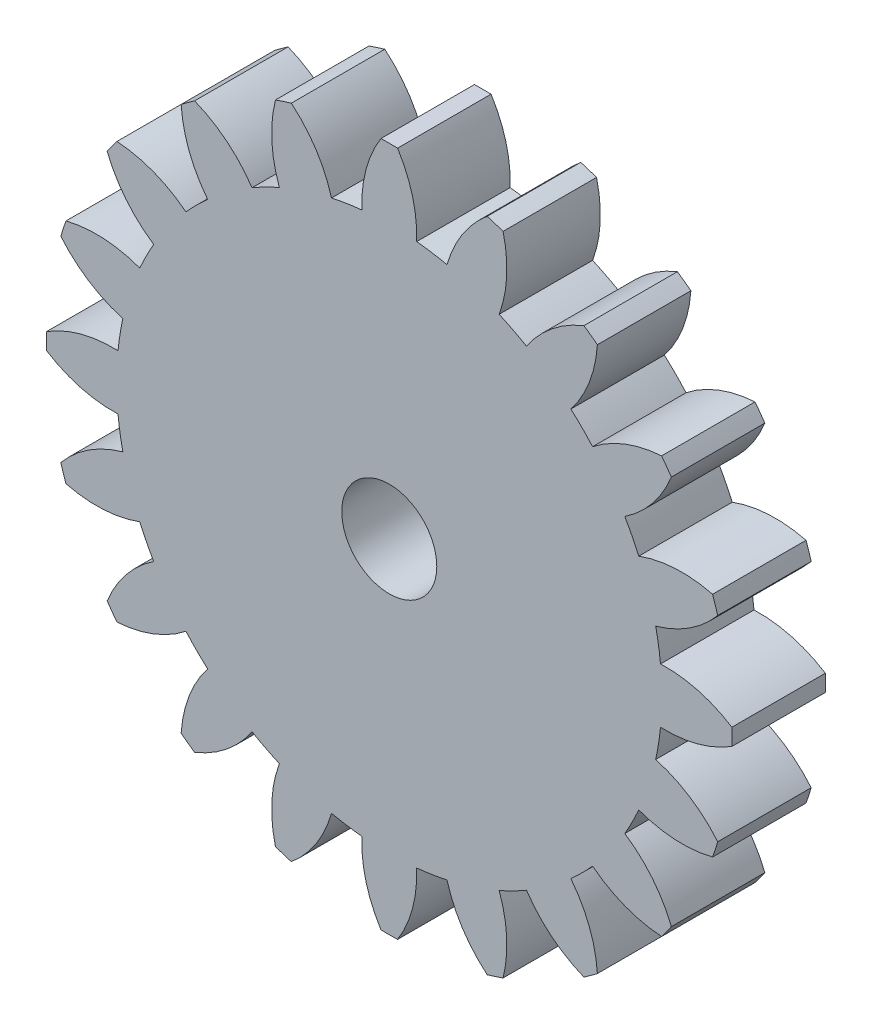
SolidWorks part; units mm, degrees
ref_plane "Front Plane" through (0, 0, 0) normal (0, 0, 1) x (1, 0, 0)
ref_plane "Top Plane" through (0, 0, 0) normal (0, 1, 0) x (1, 0, 0)
ref_plane "Right Plane" through (0, 0, 0) normal (1, 0, 0) x (0, 0, -1)
sketch "Sketch1" plane through (0, 0, 0) normal (0, 0, 1) x (1, 0, 0)
  point P0 (0, 22)
  arc B0 (12.4951, 18.1072) -> (8.8104, 15.1192) centre (15.4651, 10.679) ccw
  arc B1 (8.8104, 15.1192) -> (7.0531, 16.0147) centre (0, 0) ccw
  arc B2 (7.0531, 16.0147) -> (7.3046, 20.7519) centre (-0.4507, 18.7884) ccw
  arc B3 (7.3046, 20.7519) -> (6.2881, 21.0822) centre (0, 0) ccw
  arc B4 (6.2881, 21.0822) -> (3.7071, 17.1018) centre (11.4082, 14.9353) ccw
  arc B5 (3.7071, 17.1018) -> (1.7591, 17.4104) centre (0, 0) ccw
  arc B6 (1.7591, 17.4104) -> (0.5344, 21.9935) centre (-6.2346, 17.7296) ccw
  arc B7 (0.5344, 21.9935) -> (-0.5344, 21.9935) centre (0, 0) ccw
  arc B8 (-0.5344, 21.9935) -> (-1.7591, 17.4104) centre (6.2346, 17.7296) ccw
  arc B9 (-1.7591, 17.4104) -> (-3.7071, 17.1018) centre (0, 0) ccw
  arc B10 (-3.7071, 17.1018) -> (-6.2881, 21.0822) centre (-11.4082, 14.9353) ccw
  arc B11 (-6.2881, 21.0822) -> (-7.3046, 20.7519) centre (0, 0) ccw
  arc B12 (-7.3046, 20.7519) -> (-7.0531, 16.0147) centre (0.4507, 18.7884) ccw
  arc B13 (-7.0531, 16.0147) -> (-8.8104, 15.1192) centre (0, 0) ccw
  arc B14 (-8.8104, 15.1192) -> (-12.4951, 18.1072) centre (-15.4651, 10.679) ccw
  arc B15 (-12.4951, 18.1072) -> (-13.3598, 17.479) centre (0, 0) ccw
  arc B16 (-13.3598, 17.479) -> (-11.6567, 13.0513) centre (-5.3773, 18.0081) ccw
  arc B17 (-11.6567, 13.0513) -> (-13.0513, 11.6567) centre (0, 0) ccw
  arc B18 (-13.0513, 11.6567) -> (-17.479, 13.3598) centre (-18.0081, 5.3773) ccw
  arc B19 (-17.479, 13.3598) -> (-18.1072, 12.4951) centre (0, 0) ccw
  arc B20 (-18.1072, 12.4951) -> (-15.1192, 8.8104) centre (-10.679, 15.4651) ccw
  arc B21 (-15.1192, 8.8104) -> (-16.0147, 7.0531) centre (0, 0) ccw
  arc B22 (-16.0147, 7.0531) -> (-20.7519, 7.3046) centre (-18.7884, -0.4507) ccw
  arc B23 (-20.7519, 7.3046) -> (-21.0822, 6.2881) centre (0, 0) ccw
  arc B24 (-21.0822, 6.2881) -> (-17.1018, 3.7071) centre (-14.9353, 11.4082) ccw
  arc B25 (-17.1018, 3.7071) -> (-17.4104, 1.7591) centre (0, 0) ccw
  arc B26 (-17.4104, 1.7591) -> (-21.9935, 0.5344) centre (-17.7296, -6.2346) ccw
  arc B27 (-21.9935, 0.5344) -> (-21.9935, -0.5344) centre (0, 0) ccw
  arc B28 (-21.9935, -0.5344) -> (-17.4104, -1.7591) centre (-17.7296, 6.2346) ccw
  arc B29 (-17.4104, -1.7591) -> (-17.1018, -3.7071) centre (0, 0) ccw
  arc B30 (-17.1018, -3.7071) -> (-21.0822, -6.2881) centre (-14.9353, -11.4082) ccw
  arc B31 (-21.0822, -6.2881) -> (-20.7519, -7.3046) centre (0, 0) ccw
  arc B32 (-20.7519, -7.3046) -> (-16.0147, -7.0531) centre (-18.7884, 0.4507) ccw
  arc B33 (-16.0147, -7.0531) -> (-15.1192, -8.8104) centre (0, 0) ccw
  arc B34 (-15.1192, -8.8104) -> (-18.1072, -12.4951) centre (-10.679, -15.4651) ccw
  arc B35 (-18.1072, -12.4951) -> (-17.479, -13.3598) centre (0, 0) ccw
  arc B36 (-17.479, -13.3598) -> (-13.0513, -11.6567) centre (-18.0081, -5.3773) ccw
  arc B37 (-13.0513, -11.6567) -> (-11.6567, -13.0513) centre (0, 0) ccw
  arc B38 (-11.6567, -13.0513) -> (-13.3598, -17.479) centre (-5.3773, -18.0081) ccw
  arc B39 (-13.3598, -17.479) -> (-12.4951, -18.1072) centre (0, 0) ccw
  arc B40 (-12.4951, -18.1072) -> (-8.8104, -15.1192) centre (-15.4651, -10.679) ccw
  arc B41 (-8.8104, -15.1192) -> (-7.0531, -16.0147) centre (0, 0) ccw
  arc B42 (-7.0531, -16.0147) -> (-7.3046, -20.7519) centre (0.4507, -18.7884) ccw
  arc B43 (-7.3046, -20.7519) -> (-6.2881, -21.0822) centre (0, 0) ccw
  arc B44 (-6.2881, -21.0822) -> (-3.7071, -17.1018) centre (-11.4082, -14.9353) ccw
  arc B45 (-3.7071, -17.1018) -> (-1.7591, -17.4104) centre (0, 0) ccw
  arc B46 (-1.7591, -17.4104) -> (-0.5344, -21.9935) centre (6.2346, -17.7296) ccw
  arc B47 (-0.5344, -21.9935) -> (0.5344, -21.9935) centre (0, 0) ccw
  arc B48 (0.5344, -21.9935) -> (1.7591, -17.4104) centre (-6.2346, -17.7296) ccw
  arc B49 (1.7591, -17.4104) -> (3.7071, -17.1018) centre (0, 0) ccw
  arc B50 (3.7071, -17.1018) -> (6.2881, -21.0822) centre (11.4082, -14.9353) ccw
  arc B51 (6.2881, -21.0822) -> (7.3046, -20.7519) centre (0, 0) ccw
  arc B52 (7.3046, -20.7519) -> (7.0531, -16.0147) centre (-0.4507, -18.7884) ccw
  arc B53 (7.0531, -16.0147) -> (8.8104, -15.1192) centre (0, 0) ccw
  arc B54 (8.8104, -15.1192) -> (12.4951, -18.1072) centre (15.4651, -10.679) ccw
  arc B55 (12.4951, -18.1072) -> (13.3598, -17.479) centre (0, 0) ccw
  arc B56 (13.3598, -17.479) -> (11.6567, -13.0513) centre (5.3773, -18.0081) ccw
  arc B57 (11.6567, -13.0513) -> (13.0513, -11.6567) centre (0, 0) ccw
  arc B58 (13.0513, -11.6567) -> (17.479, -13.3598) centre (18.0081, -5.3773) ccw
  arc B59 (17.479, -13.3598) -> (18.1072, -12.4951) centre (0, 0) ccw
  arc B60 (18.1072, -12.4951) -> (15.1192, -8.8104) centre (10.679, -15.4651) ccw
  arc B61 (15.1192, -8.8104) -> (16.0147, -7.0531) centre (0, 0) ccw
  arc B62 (16.0147, -7.0531) -> (20.7519, -7.3046) centre (18.7884, 0.4507) ccw
  arc B63 (20.7519, -7.3046) -> (21.0822, -6.2881) centre (0, 0) ccw
  arc B64 (21.0822, -6.2881) -> (17.1018, -3.7071) centre (14.9353, -11.4082) ccw
  arc B65 (17.1018, -3.7071) -> (17.4104, -1.7591) centre (0, 0) ccw
  arc B66 (17.4104, -1.7591) -> (21.9935, -0.5344) centre (17.7296, 6.2346) ccw
  arc B67 (21.9935, -0.5344) -> (21.9935, 0.5344) centre (0, 0) ccw
  arc B68 (21.9935, 0.5344) -> (17.4104, 1.7591) centre (17.7296, -6.2346) ccw
  arc B69 (17.4104, 1.7591) -> (17.1018, 3.7071) centre (0, 0) ccw
  arc B70 (17.1018, 3.7071) -> (21.0822, 6.2881) centre (14.9353, 11.4082) ccw
  arc B71 (21.0822, 6.2881) -> (20.7519, 7.3046) centre (0, 0) ccw
  arc B72 (20.7519, 7.3046) -> (16.0147, 7.0531) centre (18.7884, -0.4507) ccw
  arc B73 (16.0147, 7.0531) -> (15.1192, 8.8104) centre (0, 0) ccw
  arc B74 (15.1192, 8.8104) -> (18.1072, 12.4951) centre (10.679, 15.4651) ccw
  arc B75 (18.1072, 12.4951) -> (17.479, 13.3598) centre (0, 0) ccw
  arc B76 (17.479, 13.3598) -> (13.0513, 11.6567) centre (18.0081, 5.3773) ccw
  arc B77 (13.0513, 11.6567) -> (11.6567, 13.0513) centre (0, 0) ccw
  arc B78 (11.6567, 13.0513) -> (13.3598, 17.479) centre (5.3773, 18.0081) ccw
  arc B79 (13.3598, 17.479) -> (12.4951, 18.1072) centre (0, 0) ccw
  circle B80 centre (0, 0) radius 2
sketch_block_instance "Block1-1"
sketch_block "Block1"
extrude "Boss-Extrude1" add sketch "Sketch1" along normal blind 6
sketch "Sketch2" plane through (0, 0, 6) normal (0, 0, 1) x (1, 0, 0)
  circle A0 centre (0, 0) radius 5.1392
extrude "Boss-Extrude2" add sketch "Sketch2" against normal up to surface (6 mm away) up to face at (0, 0, 0)
sketch "Sketch3" plane through (0, 0, 6) normal (0, 0, 1) x (1, 0, 0)
  circle A0 centre (0, 0) radius 3.05
  dimension "D1" = 6.1
extrude "Cut-Extrude1" cut sketch "Sketch3" against normal blind 10
